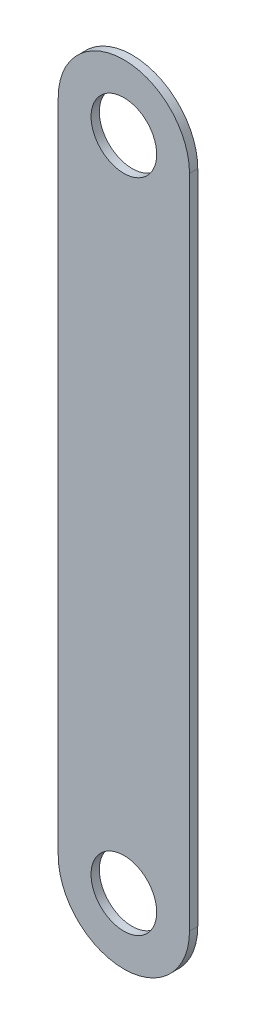
SolidWorks part; units mm, degrees
ref_plane "Front Plane" through (0, 0, 0) normal (0, 0, 1) x (1, 0, 0)
ref_plane "Top Plane" through (0, 0, 0) normal (0, 1, 0) x (1, 0, 0)
ref_plane "Right Plane" through (0, 0, 0) normal (1, 0, 0) x (0, 0, -1)
sketch "Sketch1" plane through (0, 0, 0) normal (0, 0, 1) x (1, 0, 0)
  line L0 (0, 0) -> (0, 127) construction
  line L1 (-12.7, 0) -> (-12.7, 127)
  line L2 (12.7, 0) -> (12.7, 127)
  arc A0 (-12.7, 0) -> (12.7, 0) centre (0, 0) ccw
  arc A1 (12.7, 127) -> (-12.7, 127) centre (0, 127) ccw
  circle A2 centre (0, 0) radius 6.35
  circle A3 centre (0, 127) radius 6.35
  point P3 (0, 63.5)
  dimension "D2" = 12.7
  dimension "D3" = 12.7
  dimension "D1" = 127
extrude "Boss-Extrude1" add sketch "Sketch1" along normal blind 1.6002
